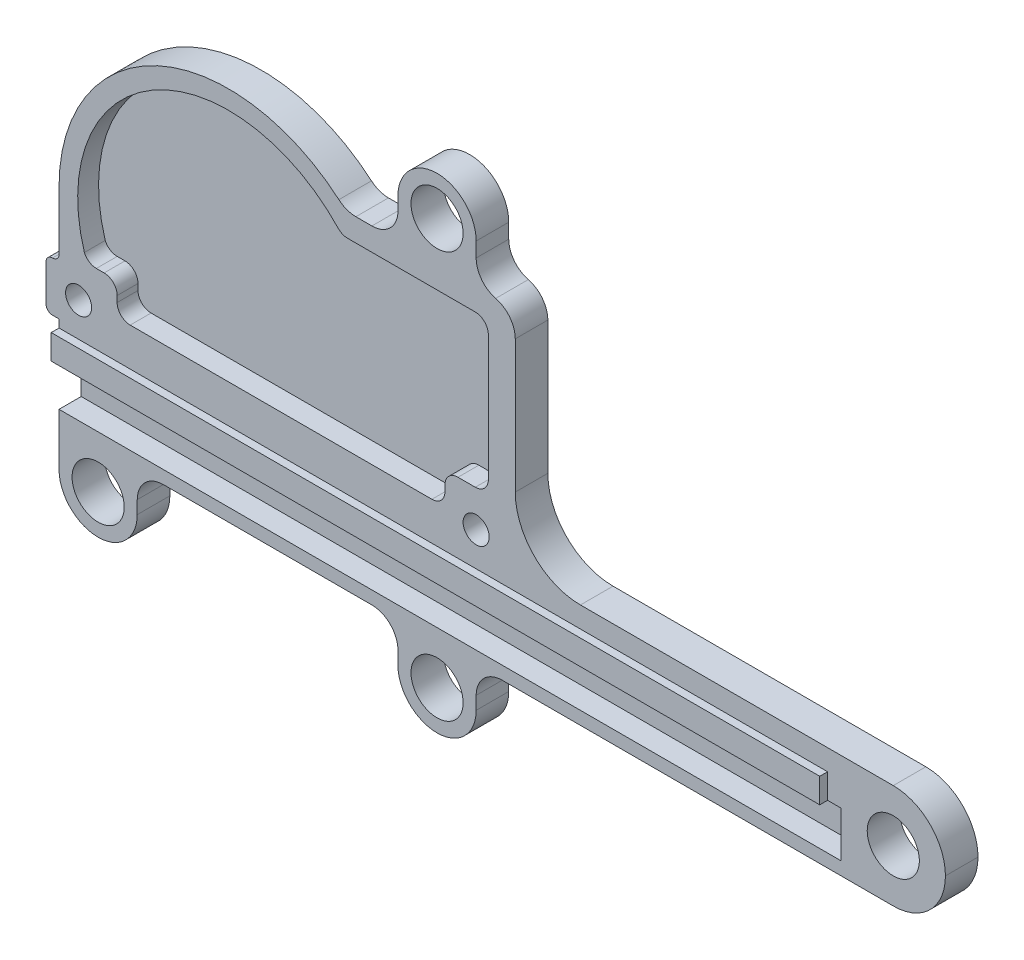
SolidWorks part; units mm, degrees
material "ABS"
ref_plane "Ebene vorne" through (0, 0, 0) normal (0, 0, 1) x (1, 0, 0)
ref_plane "Ebene oben" through (0, 0, 0) normal (0, 1, 0) x (1, 0, 0)
ref_plane "Ebene rechts" through (0, 0, 0) normal (1, 0, 0) x (0, 0, -1)
sketch "d-body" plane through (0, 0, 0) normal (0, 0, 1) x (1, 0, 0)
  line L0 (25.1418, 0) -> (-34.8582, 0)
  line L1 (-34.8582, 0) -> (-34.8582, 15.8)
  line L2 (-21.8582, 0) -> (-21.8582, 43.0223) construction
  line L3 (25.1418, 0) -> (25.1418, 8)
  line L4 (-34.8582, 15.8) -> (57.1499, 15.8) construction
  line L5 (25.1418, 8) -> (0.1418, 8)
  line L6 (0.1418, 8) -> (0.1418, 25.1808)
  line L7 (0.1418, 25.1808) -> (-12.8582, 25.1808)
  arc A0 (-34.8582, 15.8) -> (-21.8582, 28.8) centre (-21.8582, 15.8) cw
  arc A1 (-21.8582, 28.8) -> (-12.8582, 25.1808) centre (-21.8582, 15.8) cw
  dimension "D5" = 13
  dimension "D1" = 60
  dimension "D2" = 15.8
  dimension "D3" = 8
  dimension "D4" = 13
  dimension "D6" = 25
  dimension "D7" = 13
extrude "Aufsatz-Linear austragen1" add sketch "d-body" along normal blind 2.5
fillet "Verrundung1" radius 2 1 edges at (0.1418, 25.1808, 1.25)
fillet "Verrundung2" radius 5 1 edges at (0.1418, 8, 1.25)
sketch "Skizze2" plane through (0, 0, 2.5) normal (0, 0, 1) x (1, 0, 0)
  line L0 (-34.8582, 15.8) -> (-34.8582, 0) construction
  line L1 (-34.8582, 7) -> (25.1418, 7)
  line L2 (-34.8582, 7) -> (-34.8582, 1)
  line L3 (-34.8582, 1) -> (25.1418, 1)
  line L4 (25.1418, 7) -> (25.1418, 1)
  line L5 (25.1418, 0) -> (25.1418, 8) construction
  line L6 (-34.8582, 0) -> (25.1418, 0) construction
  dimension "D1" = 1
  dimension "D2" = 6
extrude "Schnitt-Linear austragen1" cut sketch "Skizze2" against normal blind 1.7
sketch "Skizze3" plane through (0, 0, 0.8) normal (0, 0, 1) x (1, 0, 0)
  line L0 (25.1418, 1) -> (25.1418, 7) construction
  line L1 (-34.8582, 7) -> (25.1418, 7)
  line L2 (-34.8582, 7) -> (-34.8582, 4.5)
  line L3 (-34.8582, 4.5) -> (25.1418, 4.5)
  line L4 (25.1418, 7) -> (25.1418, 4.5)
  dimension "D1" = 2.5
extrude "Aufsatz-Linear austragen3" add sketch "Skizze3" along normal blind 2.3
sketch "Skizze5" plane through (0, 0, 0) normal (0, 0, -1) x (-1, 0, 0)
  line L0 (34.8582, 0) -> (-25.1418, 0) construction
  line L1 (34.8582, 15.8) -> (34.8582, 0) construction
  circle A0 centre (33.3582, 9) radius 1
  dimension "D1" = 9
  dimension "D3" = 2
  dimension "D2" = 1.5
extrude "Schnitt-Linear austragen3" cut sketch "Skizze5" against normal blind 2.5
sketch "Skizze6" plane through (0, 0, 0) normal (0, 0, -1) x (-1, 0, 0)
  line L0 (34.8582, 0) -> (-25.1418, 0) construction
  line L1 (-0.1418, 13) -> (-0.1418, 23.1808) construction
  circle A0 centre (2.8582, 9) radius 1
  dimension "D1" = 9
  dimension "D3" = 2
  dimension "D2" = 3
extrude "Schnitt-Linear austragen4" cut sketch "Skizze6" against normal blind 2.5
sketch "Skizze7" plane through (0, 0, 0) normal (0, 0, -1) x (-1, 0, 0)
  line L1 (-25.1418, 8) -> (-33.1418, 8)
  line L2 (-25.1418, 8) -> (-25.1418, 0)
  line L3 (-25.1418, 0) -> (-33.1418, 0)
  line L4 (-33.1418, 8) -> (-33.1418, 0)
  circle A0 centre (-29.1418, 4) radius 2
  dimension "D2" = 4
  dimension "D1" = 8
  dimension "D3" = 4
  dimension "D4" = 4
extrude "Aufsatz-Linear austragen4" add sketch "Skizze7" against normal blind 2.5
fillet "Verrundung3" radius 4 2 edges at (33.1418, 0, 1.25) (33.1418, 8, 1.25)
sketch "Skizze8" plane through (0, 0, 3.1) normal (0, 0, 1) x (1, 0, 0)
  line L0 (25.1418, 7) -> (-34.8582, 7) construction
  line L1 (24.1007, 7) -> (25.1418, 7)
  line L2 (24.1007, 7) -> (24.1007, 4.5)
  line L3 (24.1007, 4.5) -> (25.1418, 4.5)
  line L4 (25.1418, 7) -> (25.1418, 4.5)
  line L5 (-34.8582, 4.5) -> (25.1418, 4.5) construction
  line L6 (-34.8582, 4.5) -> (25.1418, 4.5) construction
extrude "Schnitt-Linear austragen5" cut sketch "Skizze8" against normal blind 0.6
sketch "Skizze10" plane through (0, 0, 3.1) normal (0, 0, 1) x (1, 0, 0)
  line L0 (24.1007, 7) -> (24.1007, 4.5) construction
  line L1 (-34.8582, 7) -> (24.1007, 7)
  line L2 (-34.8582, 7) -> (-34.8582, 6.4)
  line L3 (-34.8582, 6.4) -> (24.1007, 6.4)
  line L4 (24.1007, 7) -> (24.1007, 6.4)
  dimension "D1" = 0.6
extrude "Schnitt-Linear austragen6" cut sketch "Skizze10" against normal blind 0.6
sketch "SkizzeStutzenInnen" plane through (0, 0, 2.5) normal (0, 0, 1) x (1, 0, 0)
  line L0 (-8.8582, 25.1808) -> (-8.8582, 28.1808)
  line L1 (-1.8582, 25.1808) -> (-12.8582, 25.1808) construction
  line L2 (-2.8582, 25.1808) -> (-2.8582, 28.1808)
  line L3 (-34.8582, 15.8) -> (-34.8582, 6.4) construction
  line L4 (-8.8582, 25.1808) -> (-2.8582, 25.1808)
  line L5 (-8.8582, 0) -> (-8.8582, -3)
  line L6 (-34.8582, 0) -> (29.1418, 0) construction
  line L7 (-2.8582, 0) -> (-2.8582, -3)
  line L8 (-8.8582, 0) -> (-2.8582, 0)
  arc A0 (-8.8582, 28.1808) -> (-2.8582, 28.1808) centre (-5.8582, 28.1808) cw
  circle A1 centre (-5.8582, 28.1808) radius 2
  arc A2 (-8.8582, -3) -> (-2.8582, -3) centre (-5.8582, -3) ccw
  circle A3 centre (-5.8582, -3) radius 2
  dimension "D4" = 4
  dimension "D7" = 4
  dimension "D1" = 6
  dimension "D2" = 3
  dimension "D3" = 26
  dimension "D5" = 6
  dimension "D6" = 3
  dimension "D8" = 26
sketch "Skizze11" plane through (0, 0, 2.5) normal (0, 0, 1) x (1, 0, 0)
  line L0 (-30.3997, 9.3243) -> (-5.2524, 9.3243)
  line L1 (-5.2524, 9.3243) -> (-5.2524, 11.789)
  line L2 (-5.2524, 11.789) -> (-1.9237, 11.789)
  line L3 (-1.9237, 11.789) -> (-1.9237, 23.4312)
  line L4 (-1.9237, 23.4312) -> (-13.1631, 23.4312)
  line L5 (-30.3997, 9.3243) -> (-30.3997, 11.789)
  line L6 (-30.3997, 11.789) -> (-32.9135, 11.789)
  line L7 (-32.9135, 11.789) -> (-32.9135, 12.3908)
  line L8 (-21.8582, 28.8) -> (-21.8582, 15.8) construction
  line L9 (-21.8582, 15.8) -> (-34.8582, 15.8) construction
  arc A0 (-12.8582, 25.1808) -> (-34.8582, 15.8) centre (-21.8582, 15.8) ccw construction
  arc A1 (-32.9135, 12.3908) -> (-13.1631, 23.4312) centre (-21.8582, 15.8) cw
extrude "Schnitt-Linear austragen7" cut sketch "Skizze11" against normal blind 1.6
extrude "Aufsatz-Linear austragen5" add sketch "SkizzeStutzenInnen" against normal blind 2.5
fillet "Verrundung4" radius 1 8 edges at (-1.9237, 23.4312, 1.7) (-13.1631, 23.4312, 1.7) (-30.3997, 11.789, 1.7) (-32.9135, 11.789, 1.7) (-30.3997, 9.3243, 1.7) (-1.9237, 11.789, 1.7) (-5.2524, 11.789, 1.7) (-5.2524, 9.3243, 1.7)
fillet "Verrundung5" radius 2 4 edges at (-8.8582, 0, 1.25) (-2.8582, 0, 1.25) (-2.8582, 25.1808, 1.25) (-8.8582, 25.1808, 1.25)
fillet "Verrundung6" radius 2 1 edges at (-12.8582, 25.1808, 1.25)
sketch "Skizze12" plane through (0, 0, 0) normal (0, 0, -1) x (-1, 0, 0)
  line L0 (34.8582, 0) -> (10.8582, 0) construction
  line L1 (28.8582, 0) -> (34.8582, 0)
  line L2 (28.8582, 0) -> (28.8582, -3)
  line L4 (34.8582, 0) -> (34.8582, -3)
  arc A0 (28.8582, -3) -> (34.8582, -3) centre (31.8582, -3) ccw
  circle A1 centre (31.8582, -3) radius 2
  dimension "D3" = 4
  dimension "D1" = 6
  dimension "D2" = 3
extrude "Aufsatz-Linear austragen6" add sketch "Skizze12" against normal blind 2.5
fillet "Verrundung7" radius 2 1 edges at (-28.8582, 0, 1.25)
sketch "Skizze13" plane through (0, 0, 0) normal (0, 0, -1) x (-1, 0, 0)
  line L0 (34.8582, 15.8) -> (34.8582, -3) construction
  line L1 (34.8582, 10.8) -> (35.8582, 10.8)
  line L2 (34.8582, 10.8) -> (34.8582, 7)
  line L3 (34.8582, 7) -> (35.8582, 7)
  line L4 (35.8582, 10.8) -> (35.8582, 7)
  dimension "D1" = 3.8
  dimension "D2" = 1
  dimension "D3" = 5
extrude "Aufsatz-Linear austragen7" add sketch "Skizze13" against normal blind 2.5
fillet "Verrundung9" radius 0.5 3 edges at (-34.8582, 10.8, 1.25) (-35.8582, 7, 1.25) (-35.8582, 10.8, 1.25)
